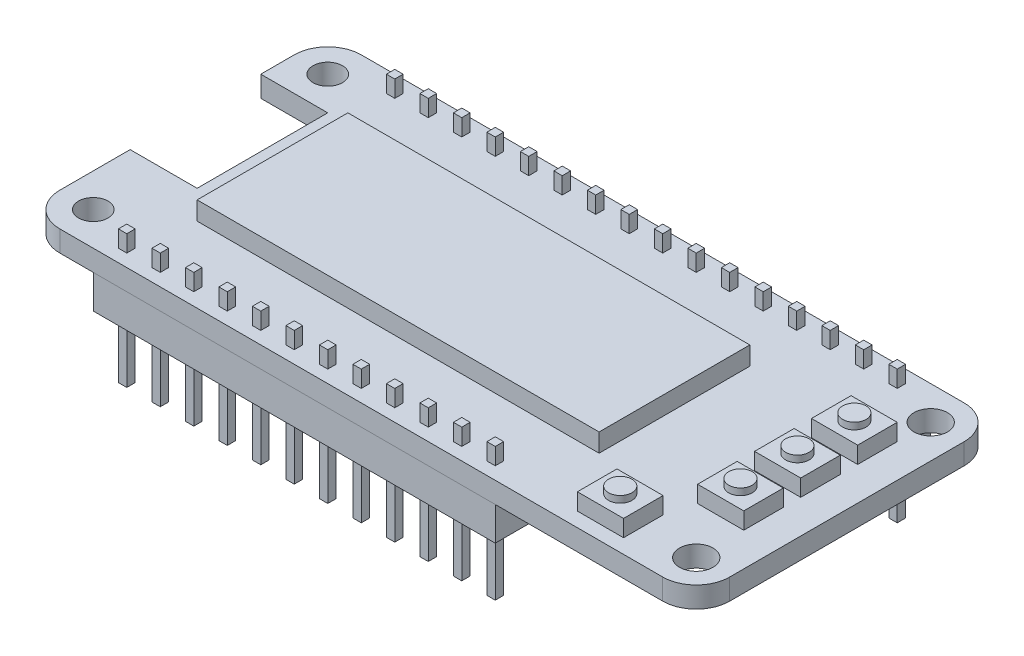
SolidWorks part; units mm, degrees
ref_plane "Front Plane" through (0, 0, 0) normal (0, 0, 1) x (1, 0, 0)
ref_plane "Top Plane" through (0, 0, 0) normal (0, 1, 0) x (1, 0, 0)
ref_plane "Right Plane" through (0, 0, 0) normal (1, 0, 0) x (0, 0, -1)
sketch "Sketch1" plane through (0, 0, 0) normal (0, 1, 0) x (1, 0, 0)
  line L0 (6.35, 1.27) -> (8.89, 1.27) construction
  line L1 (2.54, 0) -> (48.26, 0)
  line L2 (0, 2.54) -> (0, 7.874)
  line L3 (2.54, 22.86) -> (48.26, 22.86)
  line L4 (50.8, 2.54) -> (50.8, 20.32)
  line L5 (0, 17.78) -> (5.08, 17.78)
  line L6 (5.08, 17.78) -> (5.08, 7.874)
  line L7 (5.08, 7.874) -> (0, 7.874)
  line L8 (0, 17.78) -> (0, 20.32)
  arc A0 (0, 20.32) -> (2.54, 22.86) centre (2.54, 20.32) cw
  arc A1 (2.54, 0) -> (0, 2.54) centre (2.54, 2.54) cw
  arc A2 (48.26, 0) -> (50.8, 2.54) centre (48.26, 2.54) ccw
  arc A3 (48.26, 22.86) -> (50.8, 20.32) centre (48.26, 20.32) cw
  circle A4 centre (48.26, 20.32) radius 1.27
  circle A5 centre (48.26, 2.54) radius 1.27
  circle A6 centre (6.35, 21.59) radius 0.508
  circle A7 centre (8.89, 21.59) radius 0.508
  circle A8 centre (11.43, 21.59) radius 0.508
  circle A9 centre (13.97, 21.59) radius 0.508
  circle A10 centre (16.51, 21.59) radius 0.508
  circle A11 centre (19.05, 21.59) radius 0.508
  circle A12 centre (21.59, 21.59) radius 0.508
  circle A13 centre (24.13, 21.59) radius 0.508
  circle A14 centre (26.67, 21.59) radius 0.508
  circle A15 centre (29.21, 21.59) radius 0.508
  circle A16 centre (31.75, 21.59) radius 0.508
  circle A17 centre (34.29, 21.59) radius 0.508
  circle A18 centre (36.83, 21.59) radius 0.508
  circle A19 centre (39.37, 21.59) radius 0.508
  circle A20 centre (41.91, 21.59) radius 0.508
  circle A21 centre (44.45, 21.59) radius 0.508
  circle A22 centre (2.54, 20.32) radius 1.1176
  circle A23 centre (2.54, 2.54) radius 1.1176
  circle A24 centre (6.35, 1.27) radius 0.508
  circle A25 centre (8.89, 1.27) radius 0.508
  circle A26 centre (11.43, 1.27) radius 0.508
  circle A27 centre (13.97, 1.27) radius 0.508
  circle A28 centre (16.51, 1.27) radius 0.508
  circle A29 centre (19.05, 1.27) radius 0.508
  circle A30 centre (21.59, 1.27) radius 0.508
  circle A31 centre (24.13, 1.27) radius 0.508
  circle A32 centre (26.67, 1.27) radius 0.508
  circle A33 centre (29.21, 1.27) radius 0.508
  circle A34 centre (31.75, 1.27) radius 0.508
  circle A35 centre (34.29, 1.27) radius 0.508
  point P7 (0, 22.86)
  point P10 (0, 0)
  point P13 (50.8, 0)
  dimension "D3" = 2.54
  dimension "D4" = 2.54
  dimension "D5" = 1.27
  dimension "D6" = 1.016
  dimension "D10" = 2.2352
  dimension "D11" = 1.27
  dimension "D1" = 50.8
  dimension "D2" = 22.86
  dimension "D7" = 6.35
  dimension "D9" = 2.54
  dimension "D13" = 2.54
  dimension "D14" = 9.906
  dimension "D15" = 5.08
  dimension "D16" = 5.08
  dimension "D8" = 16
  dimension "D12" = 12
extrude "Boss-Extrude1" add sketch "Sketch1" along normal blind 1.5875 contours A23 | A22 | A4 | A5 | L2 L7 L6 L5 L8 A0 L3 A3 L4 A2 L1 A1 region at (48.26, 0, -20.32) region at (48.26, 0, -2.54) region at (2.54, 0, -20.32) region at (2.54, 0, -2.54)
sketch "Sketch2" plane through (0, 0, 0) normal (0, 1, 0) x (1, 0, 0)
  line L0 (8.5725, 0.9525) -> (9.2075, 0.9525)
  line L1 (6.0325, 0.9525) -> (6.6675, 0.9525)
  line L2 (6.0325, 0.9525) -> (6.0325, 1.5875)
  line L3 (6.0325, 1.5875) -> (6.6675, 1.5875)
  line L4 (6.6675, 0.9525) -> (6.6675, 1.5875)
  line L5 (6.0325, 0.9525) -> (6.6675, 1.5875) construction
  line L6 (6.0325, 1.5875) -> (6.6675, 0.9525) construction
  line L7 (9.2075, 0.9525) -> (9.2075, 1.5875)
  line L8 (8.5725, 1.5875) -> (9.2075, 1.5875)
  line L9 (8.5725, 0.9525) -> (8.5725, 1.5875)
  line L10 (11.1125, 0.9525) -> (11.7475, 0.9525)
  line L11 (11.7475, 0.9525) -> (11.7475, 1.5875)
  line L12 (11.1125, 1.5875) -> (11.7475, 1.5875)
  line L13 (11.1125, 0.9525) -> (11.1125, 1.5875)
  line L14 (13.6525, 0.9525) -> (14.2875, 0.9525)
  line L15 (14.2875, 0.9525) -> (14.2875, 1.5875)
  line L16 (13.6525, 1.5875) -> (14.2875, 1.5875)
  line L17 (13.6525, 0.9525) -> (13.6525, 1.5875)
  line L18 (16.1925, 0.9525) -> (16.8275, 0.9525)
  line L19 (16.8275, 0.9525) -> (16.8275, 1.5875)
  line L20 (16.1925, 1.5875) -> (16.8275, 1.5875)
  line L21 (16.1925, 0.9525) -> (16.1925, 1.5875)
  line L22 (18.7325, 0.9525) -> (19.3675, 0.9525)
  line L23 (19.3675, 0.9525) -> (19.3675, 1.5875)
  line L24 (18.7325, 1.5875) -> (19.3675, 1.5875)
  line L25 (18.7325, 0.9525) -> (18.7325, 1.5875)
  line L26 (21.2725, 0.9525) -> (21.9075, 0.9525)
  line L27 (21.9075, 0.9525) -> (21.9075, 1.5875)
  line L28 (21.2725, 1.5875) -> (21.9075, 1.5875)
  line L29 (21.2725, 0.9525) -> (21.2725, 1.5875)
  line L30 (23.8125, 0.9525) -> (24.4475, 0.9525)
  line L31 (24.4475, 0.9525) -> (24.4475, 1.5875)
  line L32 (23.8125, 1.5875) -> (24.4475, 1.5875)
  line L33 (23.8125, 0.9525) -> (23.8125, 1.5875)
  line L34 (26.3525, 0.9525) -> (26.9875, 0.9525)
  line L35 (26.9875, 0.9525) -> (26.9875, 1.5875)
  line L36 (26.3525, 1.5875) -> (26.9875, 1.5875)
  line L37 (26.3525, 0.9525) -> (26.3525, 1.5875)
  line L38 (28.8925, 0.9525) -> (29.5275, 0.9525)
  line L39 (29.5275, 0.9525) -> (29.5275, 1.5875)
  line L40 (28.8925, 1.5875) -> (29.5275, 1.5875)
  line L41 (28.8925, 0.9525) -> (28.8925, 1.5875)
  line L42 (31.4325, 0.9525) -> (32.0675, 0.9525)
  line L43 (32.0675, 0.9525) -> (32.0675, 1.5875)
  line L44 (31.4325, 1.5875) -> (32.0675, 1.5875)
  line L45 (31.4325, 0.9525) -> (31.4325, 1.5875)
  line L46 (33.9725, 0.9525) -> (34.6075, 0.9525)
  line L47 (34.6075, 0.9525) -> (34.6075, 1.5875)
  line L48 (33.9725, 1.5875) -> (34.6075, 1.5875)
  line L49 (33.9725, 0.9525) -> (33.9725, 1.5875)
  line L50 (9.2075, 21.9075) -> (9.2075, 21.2725)
  line L51 (6.0325, 21.9075) -> (6.6675, 21.9075)
  line L52 (6.0325, 21.9075) -> (6.0325, 21.2725)
  line L53 (6.0325, 21.2725) -> (6.6675, 21.2725)
  line L54 (6.6675, 21.9075) -> (6.6675, 21.2725)
  line L55 (6.0325, 21.9075) -> (6.6675, 21.2725) construction
  line L56 (6.0325, 21.2725) -> (6.6675, 21.9075) construction
  line L57 (8.5725, 21.2725) -> (9.2075, 21.2725)
  line L58 (8.5725, 21.9075) -> (8.5725, 21.2725)
  line L59 (8.5725, 21.9075) -> (9.2075, 21.9075)
  line L60 (11.7475, 21.9075) -> (11.7475, 21.2725)
  line L61 (11.1125, 21.2725) -> (11.7475, 21.2725)
  line L62 (11.1125, 21.9075) -> (11.1125, 21.2725)
  line L63 (11.1125, 21.9075) -> (11.7475, 21.9075)
  line L64 (14.2875, 21.9075) -> (14.2875, 21.2725)
  line L65 (13.6525, 21.2725) -> (14.2875, 21.2725)
  line L66 (13.6525, 21.9075) -> (13.6525, 21.2725)
  line L67 (13.6525, 21.9075) -> (14.2875, 21.9075)
  line L68 (16.8275, 21.9075) -> (16.8275, 21.2725)
  line L69 (16.1925, 21.2725) -> (16.8275, 21.2725)
  line L70 (16.1925, 21.9075) -> (16.1925, 21.2725)
  line L71 (16.1925, 21.9075) -> (16.8275, 21.9075)
  line L72 (19.3675, 21.9075) -> (19.3675, 21.2725)
  line L73 (18.7325, 21.2725) -> (19.3675, 21.2725)
  line L74 (18.7325, 21.9075) -> (18.7325, 21.2725)
  line L75 (18.7325, 21.9075) -> (19.3675, 21.9075)
  line L76 (21.9075, 21.9075) -> (21.9075, 21.2725)
  line L77 (21.2725, 21.2725) -> (21.9075, 21.2725)
  line L78 (21.2725, 21.9075) -> (21.2725, 21.2725)
  line L79 (21.2725, 21.9075) -> (21.9075, 21.9075)
  line L80 (24.4475, 21.9075) -> (24.4475, 21.2725)
  line L81 (23.8125, 21.2725) -> (24.4475, 21.2725)
  line L82 (23.8125, 21.9075) -> (23.8125, 21.2725)
  line L83 (23.8125, 21.9075) -> (24.4475, 21.9075)
  line L84 (26.9875, 21.9075) -> (26.9875, 21.2725)
  line L85 (26.3525, 21.2725) -> (26.9875, 21.2725)
  line L86 (26.3525, 21.9075) -> (26.3525, 21.2725)
  line L87 (26.3525, 21.9075) -> (26.9875, 21.9075)
  line L88 (29.5275, 21.9075) -> (29.5275, 21.2725)
  line L89 (28.8925, 21.2725) -> (29.5275, 21.2725)
  line L90 (28.8925, 21.9075) -> (28.8925, 21.2725)
  line L91 (28.8925, 21.9075) -> (29.5275, 21.9075)
  line L92 (32.0675, 21.9075) -> (32.0675, 21.2725)
  line L93 (31.4325, 21.2725) -> (32.0675, 21.2725)
  line L94 (31.4325, 21.9075) -> (31.4325, 21.2725)
  line L95 (31.4325, 21.9075) -> (32.0675, 21.9075)
  line L96 (34.6075, 21.9075) -> (34.6075, 21.2725)
  line L97 (33.9725, 21.2725) -> (34.6075, 21.2725)
  line L98 (33.9725, 21.9075) -> (33.9725, 21.2725)
  line L99 (33.9725, 21.9075) -> (34.6075, 21.9075)
  line L100 (37.1475, 21.9075) -> (37.1475, 21.2725)
  line L101 (36.5125, 21.2725) -> (37.1475, 21.2725)
  line L102 (36.5125, 21.9075) -> (36.5125, 21.2725)
  line L103 (36.5125, 21.9075) -> (37.1475, 21.9075)
  line L104 (39.6875, 21.9075) -> (39.6875, 21.2725)
  line L105 (39.0525, 21.2725) -> (39.6875, 21.2725)
  line L106 (39.0525, 21.9075) -> (39.0525, 21.2725)
  line L107 (39.0525, 21.9075) -> (39.6875, 21.9075)
  line L108 (42.2275, 21.9075) -> (42.2275, 21.2725)
  line L109 (41.5925, 21.2725) -> (42.2275, 21.2725)
  line L110 (41.5925, 21.9075) -> (41.5925, 21.2725)
  line L111 (41.5925, 21.9075) -> (42.2275, 21.9075)
  line L112 (44.7675, 21.9075) -> (44.7675, 21.2725)
  line L113 (44.1325, 21.2725) -> (44.7675, 21.2725)
  line L114 (44.1325, 21.9075) -> (44.1325, 21.2725)
  line L115 (44.1325, 21.9075) -> (44.7675, 21.9075)
  line L116 (6.6675, 21.9075) -> (9.2075, 21.9075) construction
  point P0 (6.35, 1.27)
  point P53 (6.35, 21.59)
  dimension "D1" = 0.635
  dimension "D2" = 12
  dimension "D3" = 2.54
  dimension "D4" = 16
  dimension "D5" = 2.54
extrude "Boss-Extrude3" add sketch "Sketch2" along normal blind 2.8575 and the other way blind 7.239 separate body
sketch "Sketch3" plane through (0, 0, 0) normal (0, -1, 0) x (1, 0, 0)
  line L1 (5.08, -20.32) -> (45.72, -20.32)
  line L2 (5.08, -20.32) -> (5.08, -22.86)
  line L3 (5.08, -22.86) -> (45.72, -22.86)
  line L4 (45.72, -20.32) -> (45.72, -22.86)
  line L5 (5.08, -2.54) -> (35.56, -2.54)
  line L6 (5.08, -2.54) -> (5.08, 0)
  line L7 (5.08, 0) -> (35.56, 0)
  line L8 (35.56, -2.54) -> (35.56, 0)
  line L10 (2.54, 0) -> (48.26, 0) construction
  point P10 (5.08, -21.59)
  dimension "D1" = 40.64
  dimension "D2" = 2.54
  dimension "D3" = 1.27
  dimension "D4" = 30.48
extrude "Boss-Extrude4" add sketch "Sketch3" along normal blind 2.54 separate body
sketch "Sketch4" plane through (0, 1.5875, 0) normal (0, 1, 0) x (1, 0, 0)
  line L0 (50.8, 11.43) -> (5.08, 11.43) construction
  line L1 (7.239, 17.145) -> (37.719, 17.145)
  line L2 (7.239, 17.145) -> (7.239, 5.715)
  line L3 (7.239, 5.715) -> (37.719, 5.715)
  line L4 (37.719, 17.145) -> (37.719, 5.715)
  line L5 (50.8, 2.54) -> (50.8, 20.32) construction
  line L6 (5.08, 17.78) -> (5.08, 7.874) construction
  line L7 (0, 17.78) -> (0, 20.32) construction
  point P10 (37.719, 11.43)
  dimension "D1" = 11.43
  dimension "D2" = 30.48
  dimension "D3" = 7.239
extrude "Boss-Extrude5" add sketch "Sketch4" along normal blind 1.397
sketch "Sketch5" plane through (0, 1.5875, 0) normal (0, 1, 0) x (1, 0, 0)
  line L0 (50.8, 2.54) -> (50.8, 20.32) construction
  line L1 (44.76, 17.78) -> (48.26, 17.78)
  line L2 (44.76, 17.78) -> (44.76, 14.78)
  line L3 (44.76, 14.78) -> (48.26, 14.78)
  line L4 (48.26, 17.78) -> (48.26, 14.78)
  line L5 (2.54, 22.86) -> (48.26, 22.86) construction
  line L6 (44.76, 13.462) -> (44.76, 10.462)
  line L7 (44.76, 10.462) -> (48.26, 10.462)
  line L8 (48.26, 13.462) -> (48.26, 10.462)
  line L9 (44.76, 13.462) -> (48.26, 13.462)
  line L10 (44.76, 9.144) -> (44.76, 6.144)
  line L11 (44.76, 6.144) -> (48.26, 6.144)
  line L12 (48.26, 9.144) -> (48.26, 6.144)
  line L13 (44.76, 9.144) -> (48.26, 9.144)
  line L14 (44.76, 17.78) -> (44.76, 13.462) construction
  line L15 (2.54, 0) -> (48.26, 0) construction
  line L16 (40.696, 4.0922) -> (44.196, 4.0922)
  line L17 (40.696, 4.0922) -> (40.696, 1.0922)
  line L18 (40.696, 1.0922) -> (44.196, 1.0922)
  line L19 (44.196, 4.0922) -> (44.196, 1.0922)
  line L20 (40.696, 4.0922) -> (44.196, 1.0922) construction
  line L21 (40.696, 1.0922) -> (44.196, 4.0922) construction
  line L22 (44.76, 9.144) -> (48.26, 6.144) construction
  line L23 (44.76, 6.144) -> (48.26, 9.144) construction
  line L24 (44.76, 13.462) -> (48.26, 10.462) construction
  line L25 (44.76, 10.462) -> (48.26, 13.462) construction
  line L26 (44.76, 14.78) -> (48.26, 17.78) construction
  line L27 (44.76, 17.78) -> (48.26, 14.78) construction
  circle A0 centre (46.51, 16.28) radius 0.889
  circle A1 centre (46.51, 11.962) radius 0.889
  circle A2 centre (46.51, 7.644) radius 0.889
  circle A3 centre (42.446, 2.5922) radius 0.889
  dimension "D9" = 1.778
  dimension "D1" = 3.5
  dimension "D2" = 3
  dimension "D3" = 2.54
  dimension "D4" = 5.08
  dimension "D5" = 4.318
  dimension "D6" = 3
  dimension "D7" = 6.604
  dimension "D8" = 1.0922
extrude "Boss-Extrude6" add sketch "Sketch5" along normal blind 1.27 contours L18 L19 L16 L17 | L11 L12 L13 L10 | L7 L8 L9 L6 | L3 L4 L1 L2
extrude "Boss-Extrude8" add sketch "Sketch5<3>" along normal offset from surface (1.778 mm away) 0.508 contours A3 | A2 | A1 | A0 up to face at (46.51, 2.8575, -16.28) offset beyond the face yes
sketch "Sketch5<3>" plane through (0, 1.5875, 0) normal (0, 1, 0) x (1, 0, 0) same geometry as "Sketch5"
